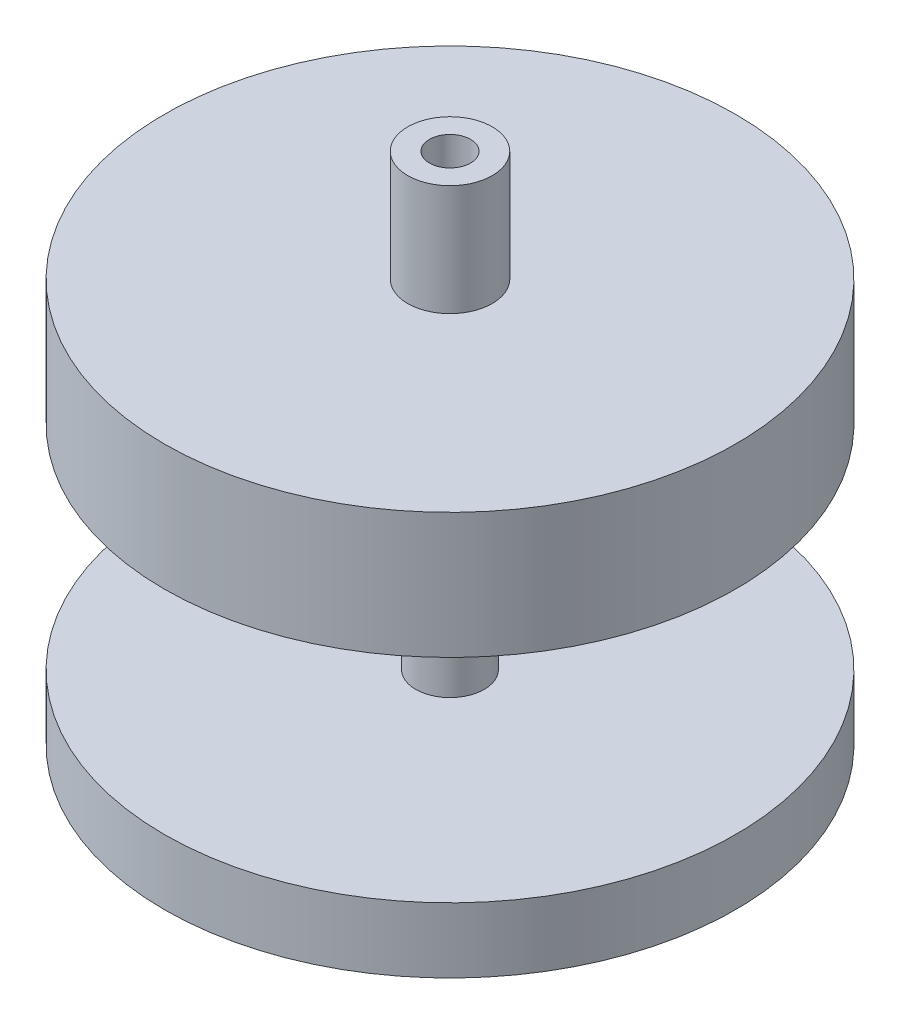
SolidWorks part; units mm, degrees
ref_plane "Front Plane" through (0, 0, 0) normal (0, 0, 1) x (1, 0, 0)
ref_plane "Top Plane" through (0, 0, 0) normal (0, 1, 0) x (1, 0, 0)
ref_plane "Right Plane" through (0, 0, 0) normal (1, 0, 0) x (0, 0, -1)
sketch "Sketch1" plane through (0, 0, 0) normal (0, 1, 0) x (1, 0, 0)
  circle A0 centre (0, 0) radius 25
extrude "Boss-Extrude1" add sketch "Sketch1" along normal blind 5.7
sketch "Sketch2" plane through (0, 5.7, 0) normal (0, 1, 0) x (1, 0, 0)
  circle A0 centre (0, 0) radius 3
extrude "Boss-Extrude2" add sketch "Sketch2" along normal blind 18.6
sketch "Sketch3" plane through (0, 24.3, 0) normal (0, 1, 0) x (1, 0, 0)
  circle A0 centre (0, 0) radius 25
extrude "Boss-Extrude3" add sketch "Sketch3" along normal blind 11 contours A0
sketch "Sketch4" plane through (0, 35.3, 0) normal (0, 1, 0) x (1, 0, 0)
  circle A0 centre (0, 0) radius 1.5
extrude "Cut-Extrude1" cut sketch "Sketch4" against normal through all
sketch "Sketch5" plane through (0, 35.3, 0) normal (0, 1, 0) x (1, 0, 0)
  circle A0 centre (0, 0) radius 3.7
extrude "Boss-Extrude4" add sketch "Sketch5" along normal blind 9.7
sketch "Sketch6" plane through (0, 45, 0) normal (0, 1, 0) x (1, 0, 0)
  circle A0 centre (0, 0) radius 1.8
extrude "Cut-Extrude2" cut sketch "Sketch6" against normal through all
